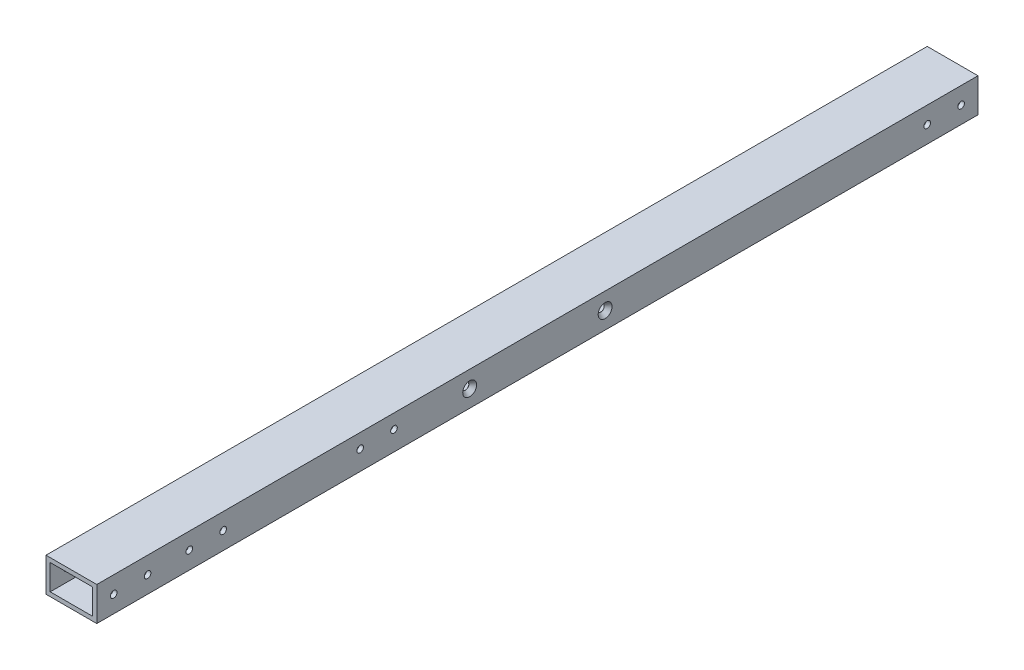
SolidWorks part; units mm, degrees
material "1060 Alloy"
ref_plane "Front Plane" through (0, 0, 0) normal (0, 0, 1) x (1, 0, 0)
ref_plane "Top Plane" through (0, 0, 0) normal (0, 1, 0) x (1, 0, 0)
ref_plane "Right Plane" through (0, 0, 0) normal (1, 0, 0) x (0, 0, -1)
sketch "Sketch1" plane through (0, 0, 0) normal (0, 0, 1) x (1, 0, 0)
  line L0 (-15.875, 9.525) -> (15.875, 9.525)
  line L2 (-19.05, 12.7) -> (19.05, 12.7)
  line L3 (-19.05, 12.7) -> (-19.05, -12.7)
  line L4 (-19.05, -12.7) -> (19.05, -12.7)
  line L5 (19.05, 12.7) -> (19.05, -12.7)
  line L10 (15.875, 9.525) -> (15.875, -9.525)
  line L11 (-15.875, -9.525) -> (15.875, -9.525)
  line L12 (-15.875, 9.525) -> (-15.875, -9.525)
  point P12 (0, 12.7)
  point P14 (19.05, 0)
  dimension "Wall Thickness" = 3.175
  dimension "Outside Width" = 38.1
  dimension "Outside Height" = 25.4
  dimension "Inside Height" = 19.05
  dimension "Inside Width" = 31.75
sketch "Sketch2" plane through (0, 0, 0) normal (1, 0, 0) x (0, 0, -1)
  line L0 (330.5556, 0) -> (-330.5556, 0)
  point P4 (0, 0)
  point P7 (-330.5556, 0)
  point P10 (330.5556, 0)
  dimension "Length" = 661.1112
sketch "Sketch3" plane through (0, 0, 0) normal (0, 0, 1) x (1, 0, 0)
  line L21 (19.05, 12.7) -> (-19.05, 12.7)
  line L22 (19.05, -12.7) -> (19.05, 12.7)
  line L23 (-19.05, -12.7) -> (19.05, -12.7)
  line L24 (-19.05, 12.7) -> (-19.05, -12.7)
  line L25 (19.05, 12.7) -> (-19.05, 12.7)
  line L26 (19.05, -12.7) -> (19.05, 12.7)
  line L27 (-19.05, -12.7) -> (19.05, -12.7)
  line L28 (-19.05, 12.7) -> (-19.05, -12.7)
  line L29 (15.875, 9.525) -> (-15.875, 9.525)
  line L30 (15.875, -9.525) -> (15.875, 9.525)
  line L31 (-15.875, -9.525) -> (15.875, -9.525)
  line L32 (-15.875, 9.525) -> (-15.875, -9.525)
  line L33 (15.875, 9.525) -> (-15.875, 9.525)
  line L34 (15.875, -9.525) -> (15.875, 9.525)
  line L35 (-15.875, -9.525) -> (15.875, -9.525)
  line L36 (-15.875, 9.525) -> (-15.875, -9.525)
  dimension "D1" = 0
  dimension "D2" = 0
extrude "Boss-Extrude1" add sketch "Sketch3" along normal up to vertex (330.5556 mm away) and the other way up to vertex (330.5556 mm away) up to point (0, 0, 330.5556) other way up to point (0, 0, -330.5556)
sketch "Drawing Reference" plane through (0, 0, 0) normal (1, 0, 0) x (0, 0, -1)
  line L0 (-330.5556, 0) -> (330.5556, 0) construction
  line L1 (0, -12.7) -> (0, 12.7) construction
  line L2 (-330.5556, -12.7) -> (330.5556, -12.7) construction
  line L5 (-330.5556, 12.7) -> (330.5556, 12.7) construction
  point P7 (-303.1236, 0)
  point P8 (303.1236, 0)
  dimension "D1" = 27.432
sketch "Sketch4" plane through (-19.05, 0, 0) normal (-1, 0, 0) x (0, 0, 1)
  line L0 (-330.5556, 0) -> (-317.8556, 0)
  line L1 (-330.5556, 12.7) -> (-330.5556, -12.7) construction
  line L2 (-317.8556, 0) -> (-292.4556, 0)
  line L3 (330.5556, 12.7) -> (330.5556, -12.7) construction
  line L4 (330.5556, 0) -> (317.8556, 0)
  line L5 (317.8556, 0) -> (292.4556, 0)
  line L6 (0, 0) -> (50.8, 0) construction
  line L7 (0, 0) -> (-50.8, 0) construction
  point P11 (-317.8556, 0)
  point P13 (-292.4556, 0)
  point P14 (317.8556, 0)
  point P15 (292.4556, 0)
hole_wizard "#10 Clearance Hole2" positions "Sketch11" profile "Sketch12" hole size "#10" standard "ANSI Inch" end condition through all
sketch "Sketch11" plane through (-19.05, 0, 0) normal (-1, 0, 0) x (0, 0, 1)
  point P0 (-317.8556, 0)
  point P3 (-292.4556, 0)
  point P6 (292.4556, 0)
  point P9 (317.8556, 0)
sketch "Sketch12" plane through (-19.05, 0, -317.8556) normal (0, 1, 0) x (0, 0, 1)
  line L0 (0, 0) -> (0, 38.1)
  line L1 (0, 38.1) -> (2.4892, 38.1)
  line L2 (2.4892, 38.1) -> (2.4892, 0)
  line L5 (2.4892, 0) -> (0, 0)
  line L11 (0, -6.35) -> (0, 107.95) construction
  dimension "Thru Hole Dia." = 4.9784
  dimension "Thru Hole Depth" = 38.1
hole_wizard "#10 Clearance Hole4" positions "Sketch14" profile "Sketch16" hole size "#10" standard "ANSI Inch" end condition through all
sketch "Sketch14" plane through (19.05, 0, 0) normal (1, 0, 0) x (0, 0, -1)
  point P33 (-261.1289, 0.3559)
  point P36 (-235.7289, 0.3559)
  point P42 (-132.9849, 1.9434)
  point P45 (-107.5849, 1.9434)
  point P48 (0, 0)
sketch "Sketch16" plane through (19.05, 0.3559, 261.1289) normal (0, 1, 0) x (0, 0, -1)
  line L0 (0, 0) -> (0, 38.1)
  line L1 (0, 38.1) -> (2.4892, 38.1)
  line L2 (2.4892, 38.1) -> (2.4892, 0)
  line L5 (2.4892, 0) -> (0, 0)
  line L11 (0, -6.35) -> (0, 107.95) construction
  dimension "Thru Hole Dia." = 4.9784
  dimension "Thru Hole Depth" = 38.1
sketch "Sketch17" plane through (19.05, 0, 0) normal (1, 0, 0) x (0, 0, -1)
  point P0 (-261.8407, 0)
  point P1 (-236.4407, 0)
hole_wizard "#10 Clearance Hole3" positions "Sketch20" profile "Sketch21" hole size "#10" standard "ANSI Inch" end condition through all
sketch "Sketch20" plane through (-19.05, 0, 0) normal (-1, 0, 0) x (0, 0, 1)
  point P0 (-50.8, 0)
  point P3 (50.8, 0)
sketch "Sketch21" plane through (-19.05, 0, -50.8) normal (0, 1, 0) x (0, 0, 1)
  line L0 (0, 0) -> (0, 38.1)
  line L1 (0, 38.1) -> (5.207, 38.1)
  line L2 (2.4892, 34.9735) -> (2.4892, 0)
  line L5 (2.4892, 0) -> (0, 0)
  line L7 (5.207, 38.1) -> (2.4892, 34.9735)
  line L8 (-5.207, 38.1) -> (-2.4892, 34.9735) construction
  line L11 (0, -6.35) -> (0, 107.95) construction
  dimension "Thru Hole Dia." = 4.9784
  dimension "Thru Hole Depth" = 38.1
  dimension "Far C'Sink Dia." = 10.414
  dimension "Far C'Sink Angle" = 82
equation "\"D1@Drawing Reference\"=\"Outside Width@Sketch1\" * 0.72"
